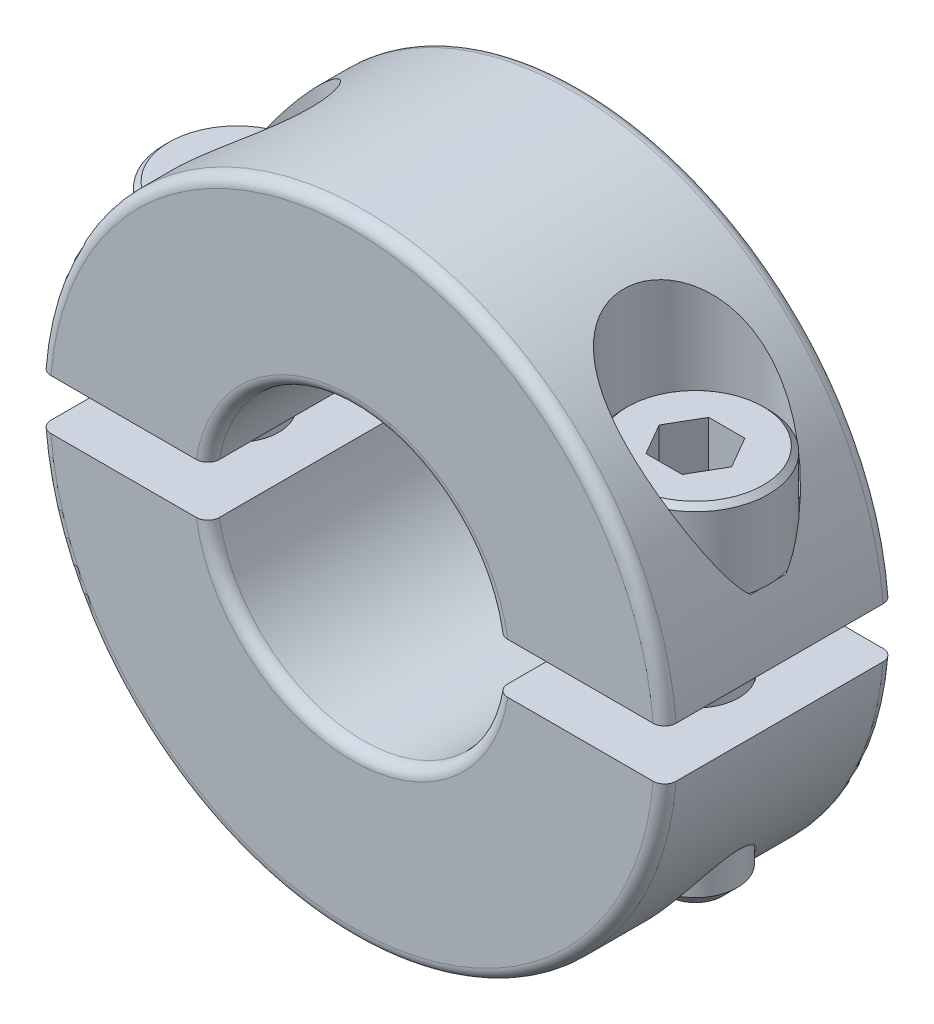
SolidWorks part; units mm, degrees
material "Cast Carbon Steel"
ref_plane "Front Plane" through (0, 0, 0) normal (0, 0, 1) x (1, 0, 0)
ref_plane "Top Plane" through (0, 0, 0) normal (0, 1, 0) x (1, 0, 0)
ref_plane "Right Plane" through (0, 0, 0) normal (1, 0, 0) x (0, 0, -1)
sketch "Sketch1" plane through (0, 0, 0) normal (0, 0, 1) x (1, 0, 0)
  line L0 (-15, 0) -> (-7, 0) construction
  line L1 (-14.9519, 1.2) -> (-6.8964, 1.2)
  line L2 (-14.9519, -1.2) -> (-6.8964, -1.2)
  line L3 (6.8964, 1.2) -> (14.9519, 1.2)
  line L4 (6.8964, -1.2) -> (14.9519, -1.2)
  line L5 (0, 0) -> (0, 15) construction
  line L6 (-11, 0) -> (-11, 1.2) construction
  line L7 (-11, 0) -> (-11, -1.2) construction
  line L8 (10.9241, 1.2) -> (10.9241, -1.2) construction
  circle A0 centre (0, 0) radius 15 construction
  circle A1 centre (0, 0) radius 7 construction
  arc A4 (-6.8964, -1.2) -> (6.8964, -1.2) centre (0, 0) ccw
  arc A5 (-14.9519, -1.2) -> (14.9519, -1.2) centre (0, 0) ccw
  arc A6 (6.8964, 1.2) -> (-6.8964, 1.2) centre (0, 0) ccw
  arc A7 (14.9519, 1.2) -> (-14.9519, 1.2) centre (0, 0) ccw
  point P4 (15, 0)
  point P14 (-15, 0)
  point P19 (-7, 0)
  point P21 (7, 0)
  dimension "Bore Dia" = 14
  dimension "OD" = 30
  dimension "Separation" = 2.4
  dimension "D1" = 21.9241
extrude "Extrude1" add sketch "Sketch1" along normal mid plane 11
fillet "Fillet1" radius 0.55 4 edges at (0, 7, 5.5) (0, 7, -5.5) (0, 15, -5.5) (0, 15, 5.5)
fillet "Fillet2" radius 0.55 4 edges at (0, -15, 5.5) (0, -7, 5.5) (0, -7, -5.5) (0, -15, -5.5)
sketch "Sketch2" plane through (0, 0, 0) normal (0, 1, 0) x (1, 0, 0)
  line L0 (0, 5.5) -> (0, -5.5) construction
  line L3 (0, 0) -> (-7, 0) construction
  line L4 (-7, 0) -> (-15, 0) construction
  line L7 (-11, 5.5) -> (-11, -5.5) construction
  line L8 (-11.1905, 5.5) -> (-10.8095, 5.5)
  line L9 (-14.4001, -5.5) -> (14.4001, -5.5) construction
  line L10 (-15, 0) -> (-7, 0) construction
  line L11 (14.4001, 5.5) -> (-14.4001, 5.5) construction
  arc A0 (-11.1905, 5.5) -> (-10.8095, 5.5) centre (-11, 5.5) ccw
  point P16 (-11, 0)
  dimension "D2" = 0.1905
revolve "Cut-Revolve1" cut sketch "Sketch2" angle 360 about L0
sketch "Sketch3" plane through (0, 0, 0) normal (0, 0, 1) x (1, 0, 0)
  line L0 (-11, 15) -> (-7.4975, 15)
  line L1 (-7.4975, 15) -> (-7.4975, 4.2)
  line L2 (-7.4975, 4.2) -> (-9, 4.2)
  line L3 (-9, 4.2) -> (-9, -15)
  line L4 (-9, -15) -> (-11, -15)
  line L5 (-11, -15) -> (-11, 15)
  line L7 (-11, 15) -> (-11, 18.5025) construction
  line L8 (-7.4975, 15) -> (0, 15) construction
  line L9 (0, -15) -> (-9, -15) construction
  line L10 (-15, 0) -> (-7, 0) construction
  line L11 (-14.9519, 1.2) -> (-6.8964, 1.2) construction
  line L12 (0, 0) -> (0, -15) construction
  line L13 (-11, 0) -> (-11, -1.2) construction
  circle A0 centre (0, 0) radius 15 construction
  circle A2 centre (0, 0) radius 7 construction
  arc A4 (-14.9519, -1.2) -> (14.9519, -1.2) centre (0, 0) ccw construction
  dimension "D3" = 3
  dimension "D1" = 7.005
revolve "Cut-Revolve2" cut sketch "Sketch3" angle 360 about L5
mirror "Mirror1" about plane through (0, 0, 0) normal (1, 0, 0) of "Cut-Revolve2"
sketch "Sketch8" plane through (0, 4.2, 0) normal (0, 1, 0) x (1, 0, 0)
  circle A0 centre (11, 0) radius 2 construction
  circle A1 centre (11, 0) radius 2
extrude "Cut-Extrude3" cut sketch "Sketch8" against normal through all
sketch "Sketch4" plane through (0, 0, 0) normal (0, 0, 1) x (1, 0, 0)
  line L0 (-11, 8.2) -> (-7.5, 8.2)
  line L2 (-7.5, 8.2) -> (-7.5, 4.2)
  line L3 (-7.5, 4.2) -> (-9, 4.2)
  line L4 (-9, 4.2) -> (-9, -9.8)
  line L5 (-9, 4.2) -> (-9, -15) construction
  line L6 (-9, -9.8) -> (-11, -9.8)
  line L7 (-11, -15) -> (-11, 15) construction
  line L8 (-11, -9.8) -> (-11, 8.2)
  line L9 (-9, -9.8) -> (-13, -9.8) construction
  line L10 (-11, 8.2) -> (-11, 11.7) construction
  dimension "Screw Lg" = 14
  dimension "Head Dia" = 7
revolve "Revolve1" add sketch "Sketch4" angle 360 about L8
sketch "Sketch5" plane through (0, 8.2, 0) normal (0, 1, 0) x (-1, 0, 0)
  line L1 (11.866, -1.5) -> (12.7321, 0)
  line L2 (12.7321, 0) -> (11.866, 1.5)
  line L3 (11.866, 1.5) -> (10.134, 1.5)
  line L4 (10.134, 1.5) -> (9.2679, 0)
  line L5 (9.2679, 0) -> (10.134, -1.5)
  line L6 (10.134, -1.5) -> (11.866, -1.5)
  circle A0 centre (11, 0) radius 1.5 construction
  dimension "Hex" = 3
extrude "Cut-Extrude2" cut sketch "Sketch5" against normal blind 3
chamfer "Chamfer1" distance 0.254 angle 45 1 edges at (-11, 8.2, -3.5)
sketch "Sketch6" plane through (0, -9.8, 0) normal (0, -1, 0) x (1, 0, 0)
  circle A0 centre (-11, 0) radius 2 construction
  circle A1 centre (-11, 0) radius 2
  point P3 (-13, 0)
curve "Helix/Spiral1" [suppressed] pitch 0.7 height 14 turns 20 parameters "Height"=14, "Pitch"=0.7
sketch "Sketch7" plane through (0, 0, 0) normal (0, 0, 1) x (1, 0, 0)
  line L0 (-13.0758, -9.7562) -> (-13.0758, -10.4562) construction
  line L1 (-13.0758, -10.4562) -> (-12.4696, -10.1062) construction
  line L2 (-12.4696, -10.1062) -> (-13.0758, -9.7562) construction
  line L3 (-13.0758, -10.1062) -> (-13, -10.1062) construction
  line L4 (-12.4696, -10.1062) -> (-12.5453, -10.1062) construction
  line L5 (-12.5453, -10.0625) -> (-12.5453, -10.15)
  line L6 (-13, -10.4125) -> (-13, -9.8) construction
  line L7 (-12.5453, -10.0625) -> (-13.0379, -9.7781)
  line L8 (-13.0379, -9.7781) -> (-13.0379, -10.4344)
  line L9 (-13.0379, -10.4344) -> (-12.5453, -10.15)
  point P10 (-13.0379, -10.1062)
  dimension "D1" = 0.7
  dimension "D2" = 0.0875
chamfer "Chamfer2" distance 0.7 angle 45 1 edges at (-11, -9.8, -2)
sweep "Cut-Sweep1" [suppressed] cut profiles "Sketch7" path "Helix/Spiral1"
pattern_linear "LPattern1" count 2 spacing 21.9241 along (1, 0, 0) of bodies 149 162
equation "\"D1@Sketch3\" = \"Head Dia@Sketch4\"+.005"
equation "\"D1@Cut-Extrude2\" =\"Hex@Sketch5\""
equation "\"D1@Fillet1\" = \"Width@Extrude1\"*.05"
equation "\"D1@Fillet2\" = \"D1@Fillet1\""
equation "\"Height@Helix/Spiral1\" = \"Screw Lg@Sketch4\""
equation "\"D1@Sketch7\" = \"Pitch@Helix/Spiral1\""
equation "\"D2@Sketch7\" = \"D1@Sketch7\"/8"
equation "\"D1@Chamfer2\" = \"Pitch@Helix/Spiral1\""
equation "\"D3@Sketch3\" = \"Screw Dia@Sketch3\"*.750"
equation "\"D3@LPattern1\" = \"D1@Sketch1\""
